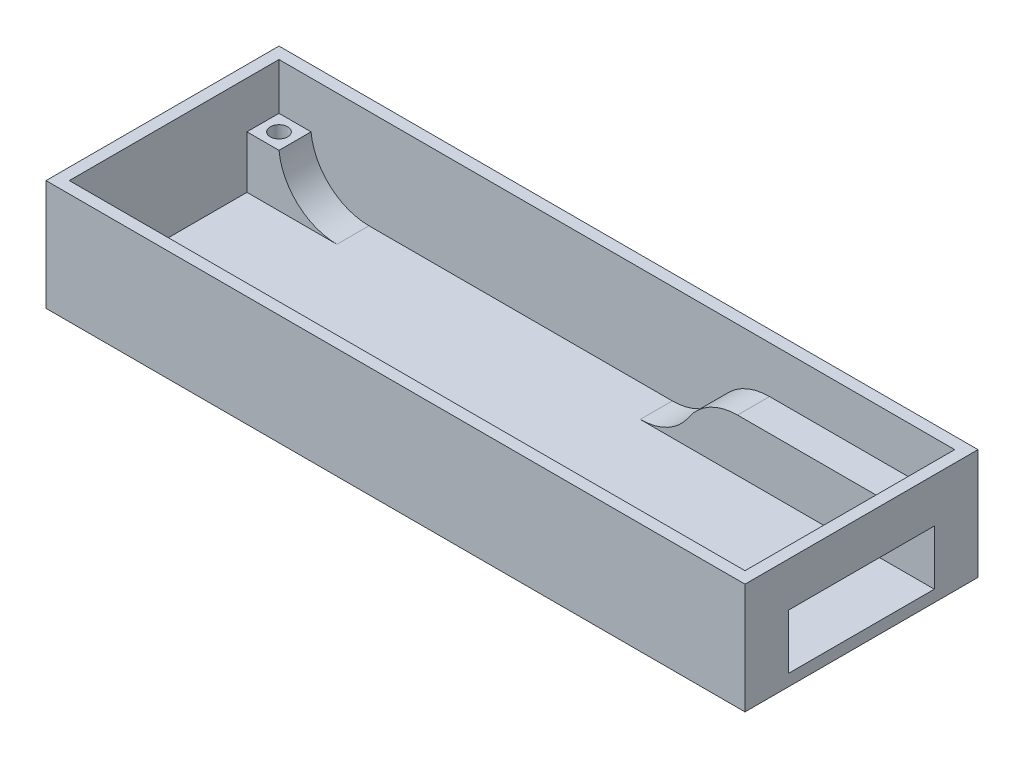
SolidWorks part; units mm, degrees
ref_plane "Front Plane" through (0, 0, 0) normal (0, 0, 1) x (1, 0, 0)
ref_plane "Top Plane" through (0, 0, 0) normal (0, 1, 0) x (1, 0, 0)
ref_plane "Right Plane" through (0, 0, 0) normal (1, 0, 0) x (0, 0, -1)
sketch "Sketch1" plane through (0, 0, 0) normal (0, 1, 0) x (1, 0, 0)
  line L0 (-30, 0) -> (30, 0) construction
  line L1 (-30, -10) -> (30, -10)
  line L2 (-30, -10) -> (-30, 10)
  line L3 (-30, 10) -> (30, 10)
  line L4 (30, -10) -> (30, 10)
  line L5 (0, 10) -> (0, -10) construction
  point P6 (0, 0)
  dimension "D1" = 20
  dimension "D2" = 60
extrude "Boss-Extrude1" add sketch "Sketch1" along normal blind 9.5
shell "Shell1" thickness 1 removed face at (0, 9.5, 0)
sketch "Sketch2" plane through (30, 0, 0) normal (1, 0, 0) x (0, 0, -1)
  line L2 (6.25, 5.7) -> (6.25, 1)
  line L3 (-9, 1) -> (9, 1) construction
  line L4 (6.25, 1) -> (-6.25, 1)
  line L5 (0, 1) -> (0, 5.7) construction
  line L6 (-6.25, 5.7) -> (-6.25, 1)
  line L7 (-6.25, 1) -> (-6.25, 5.7) construction
  line L8 (-6.25, 5.7) -> (6.25, 5.7) construction
  line L9 (-6.25, 5.7) -> (6.25, 5.7)
extrude "Cut-Extrude1" cut sketch "Sketch2" against normal blind 12
sketch "Sketch3" plane through (0, 1, 0) normal (0, 1, 0) x (1, 0, 0)
  line L0 (-29, 0) -> (29, 0) construction
  line L1 (-29, 9) -> (-29, -9) construction
  line L2 (29, -9) -> (29, 9) construction
  line L3 (29, 6.25) -> (30, 6.25) construction
  line L4 (29, 9) -> (9.7327, 9)
  line L5 (29, 9) -> (29, 6.25)
  line L6 (29, 6.25) -> (9.7327, 6.25)
  line L7 (9.7327, 9) -> (9.7327, 6.25)
  line L8 (-29, 9) -> (-26.25, 6.25) construction
  line L9 (-29, 9) -> (-26.25, 9)
  line L10 (-29, 9) -> (-29, 6.25)
  line L11 (-29, 6.25) -> (-26.25, 6.25)
  line L12 (-26.25, 9) -> (-26.25, 6.25)
  line L13 (29, 7.625) -> (26.5, 7.625) construction
  line L14 (29, -7.625) -> (26.5, -7.625) construction
  line L15 (-29, -9) -> (-26.25, -6.25) construction
  line L16 (-26.25, -9) -> (-26.25, -6.25)
  line L17 (-29, -6.25) -> (-26.25, -6.25)
  line L18 (-29, -9) -> (-29, -6.25)
  line L19 (-29, -9) -> (-26.25, -9)
  line L20 (9.7327, -9) -> (9.7327, -6.25)
  line L21 (29, -6.25) -> (9.7327, -6.25)
  line L22 (29, -9) -> (29, -6.25)
  line L23 (29, -9) -> (9.7327, -9)
  circle A0 centre (26.5, 7.625) radius 0.75
  circle A1 centre (-27.625, 7.625) radius 0.75
  circle A2 centre (26.5, -7.625) radius 0.75
  circle A3 centre (-27.625, -7.625) radius 0.75
  dimension "D1" = 2.75
extrude "Boss-Extrude2" add sketch "Sketch3" along normal blind 4.5
fillet "Fillet1" radius 5 4 edges at (-26.25, 1, 7.625) (-26.25, 1, -7.625) (9.7327, 1, 7.625) (9.7327, 1, -7.625)
fillet "Fillet2" radius 5 2 edges at (9.7327, 5.5, 7.625) (9.7327, 5.5, -7.625)
